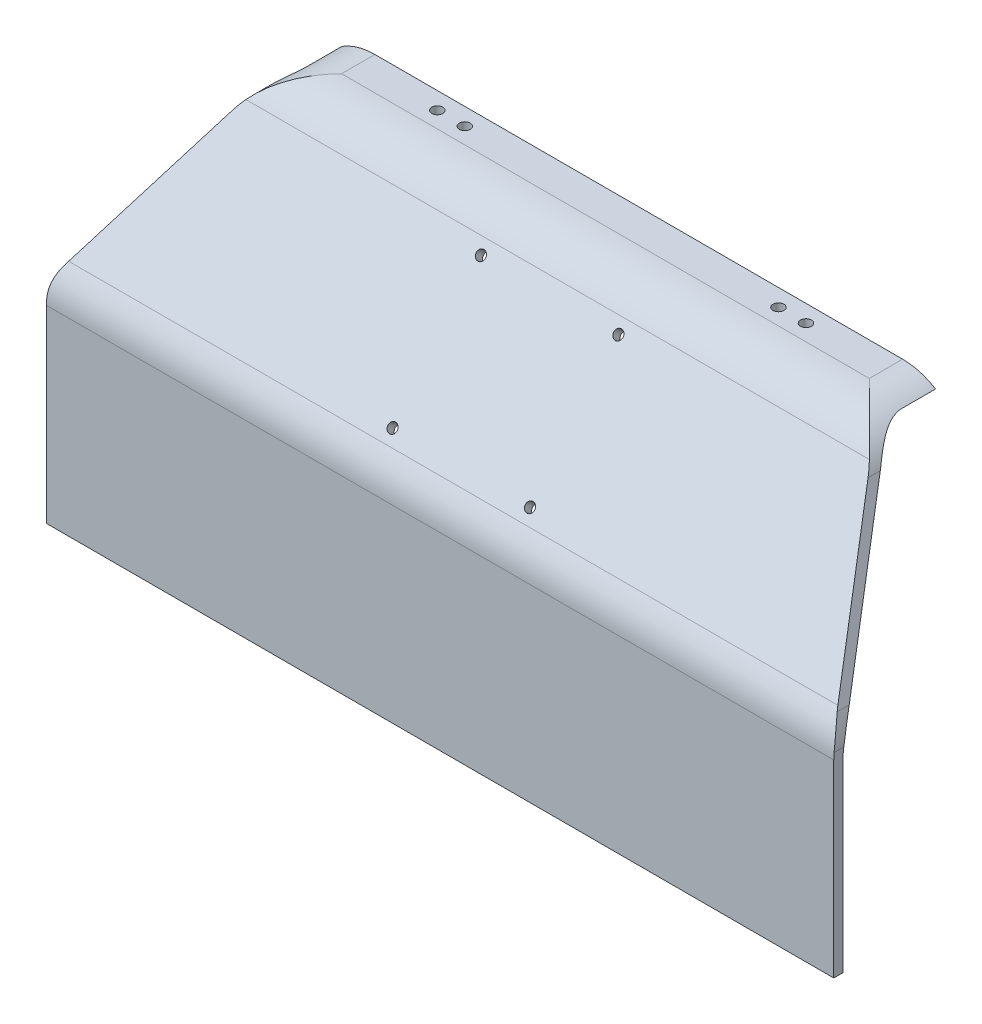
SolidWorks part; units mm, degrees
material "Acrílico (Impacto medio-alto)"
ref_plane "Alzado" through (0, 0, 0) normal (0, 0, 1) x (1, 0, 0)
ref_plane "Planta" through (0, 0, 0) normal (0, 1, 0) x (1, 0, 0)
ref_plane "Vista lateral" through (0, 0, 0) normal (1, 0, 0) x (0, 0, -1)
sketch "Croquis1" plane through (0, 0, 0) normal (1, 0, 0) x (0, 0, -1)
  line L0 (0, 0) -> (0, 66.9081)
  line L1 (0, 66.9081) -> (41.9998, 116.9615)
  line L2 (41.9998, 116.9615) -> (60.6009, 116.9615)
  line L3 (60.6009, 116.9615) -> (60.6009, 119.9615)
  line L4 (60.6009, 119.9615) -> (40.6009, 119.9615)
  line L5 (40.6009, 119.9615) -> (-3, 68)
  line L6 (-3, 68) -> (-3, 0)
  line L7 (-3, 0) -> (0, 0)
  line L8 (0, 66.9081) -> (29.2398, 66.9081) construction
  dimension "D1" = 3
  dimension "D2" = 3
  dimension "D3" = 3
  dimension "D4" = 68
  dimension "D5" = 119.9615
  dimension "D6" = 20
  dimension "D7" = 50
extrude "Saliente-Extruir1" add sketch "Croquis1" along normal mid plane 252
fillet "Redondeo1" radius 18 1 edges at (0, 68, 3)
fillet "Redondeo2" radius 20 1 edges at (0, 119.9615, -40.6009)
fillet "Redondeo3" radius 17 1 edges at (0, 116.9615, -41.9998)
fillet "Redondeo4" radius 17 1 edges at (0, 66.9081, 0)
sketch "Croquis2" plane through (0, 0, 3) normal (0, 0, 1) x (1, 0, 0)
  line L29 (-96, 119.9615) -> (-126, 68)
  line L35 (-96, 119.9615) -> (-126, 119.9615)
  line L36 (-126, 119.9615) -> (-126, 68)
  dimension "D5" = 60
extrude "Cortar-Extruir1" cut sketch "Croquis2" against normal through all
mirror "Simetría1" about plane through (0, 0, 0) normal (1, 0, 0) of "Cortar-Extruir1"
fillet "Redondeo5" radius 17 2 edges at (-126, 68, 0.064) (126, 68, 0.064)
sketch "Croquis5" plane through (0, 0, -60.6009) normal (0, 0, -1) x (-1, 0, 0)
  line L0 (84.453, 119.9615) -> (96, 119.9615)
  line L1 (96, 119.9615) -> (101.7735, 109.9615)
  arc A0 (101.7735, 109.9615) -> (84.453, 119.9615) centre (84.453, 99.9615) ccw
extrude "Cortar-Extruir2" cut sketch "Croquis5" against normal through all
mirror "Simetría2" about plane through (0, 0, 0) normal (1, 0, 0) of "Cortar-Extruir2"
sketch "Croquis6" plane through (0, 119.9615, 0) normal (0, 1, 0) x (1, 0, 0)
  circle A0 centre (-59, 55.1009) radius 1.75
  circle A1 centre (-50.2, 55.1009) radius 1.75
extrude "Cortar-Extruir3" cut sketch "Croquis6" against normal blind 20
mirror "Simetría3" about plane through (0, 0, 0) normal (1, 0, 0) of "Cortar-Extruir3"
sketch "Croquis7" plane through (0, 0, 0) normal (0, -1, 0) x (1, 0, 0)
  line L4 (-126, 3) -> (-126, 0)
  line L5 (-126, 0) -> (126, 0)
  line L6 (126, 0) -> (126, 3)
  line L7 (126, 3) -> (-126, 3)
  line L8 (-126, 3) -> (-126, 0)
  line L9 (-126, 0) -> (126, 0)
  line L10 (126, 0) -> (126, 3)
  line L11 (126, 3) -> (-126, 3)
  dimension "D1" = 0
extrude "Cortar-Extruir4" cut sketch "Croquis7" against normal blind 1
ref_axis "Eje1" through (112.438, 91.4901, -16.7105) along (-1, 0, 0)
ref_plane "Plano1" through (0, 61.9169, -51.9545) normal (0, 0.766, -0.6428) x (-1, 0, 0)
sketch "Croquis9" plane through (0, 29.5732, 35.2439) normal (0, 0.6428, 0.766) x (1, 0, 0)
  circle A0 centre (-22, 104.7141) radius 1.5
  circle A1 centre (22, 104.7141) radius 1.5
  circle A2 centre (22, 60.7141) radius 1.5
  circle A3 centre (-22, 60.7141) radius 1.5
  point P0 (22, 104.7141)
  point P1 (22, 60.7141)
  point P3 (-22, 60.7141)
  point P5 (-22, 104.7141)
  dimension "D1" = 3
extrude "Cortar-Extruir5" cut sketch "Croquis9" against normal through all
